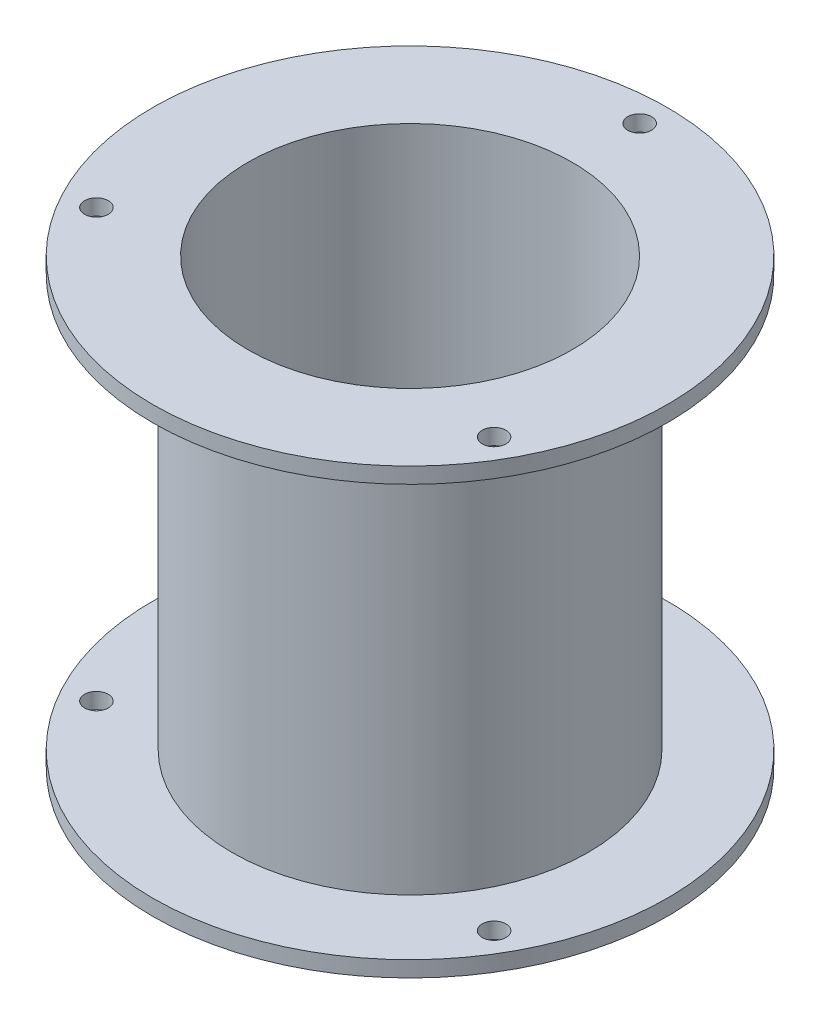
SolidWorks part; units mm, degrees
ref_plane "Front Plane" through (0, 0, 0) normal (0, 0, 1) x (1, 0, 0)
ref_plane "Top Plane" through (0, 0, 0) normal (0, 1, 0) x (1, 0, 0)
ref_plane "Right Plane" through (0, 0, 0) normal (1, 0, 0) x (0, 0, -1)
sketch "Sketch1" plane through (0, 0, 0) normal (0, 1, 0) x (1, 0, 0)
  circle A4 centre (0, 0) radius 32.5
  dimension "D5" = 65
extrude "Boss-Extrude1" add sketch "Sketch1" along normal blind 56
sketch "Sketch6" plane through (0, 56, 0) normal (0, 1, 0) x (1, 0, 0)
  circle A0 centre (0, 0) radius 22.5
  circle A1 centre (0, 0) radius 32.5 construction
  circle A2 centre (0, 0) radius 32.5
  dimension "D1" = 10
extrude "Cut-Extrude4" cut sketch "Sketch6" against normal offset from surface (52 mm away) 2 from offset 2 up to face at (0, 0, 32.5) offset against normal yes
sketch "Sketch2" plane through (0, 56, 0) normal (0, 1, 0) x (1, 0, 0)
  line L0 (0, 29) -> (0, 0) construction
  line L1 (0, 0) -> (-25.1147, -14.5) construction
  line L2 (0, 0) -> (25.1147, -14.5) construction
  circle A0 centre (0, 0) radius 29 construction
  circle A1 centre (0, 29) radius 1.5
  circle A2 centre (-25.1147, -14.5) radius 1.5
  circle A3 centre (25.1147, -14.5) radius 1.5
  point P9 (0, 29)
  point P10 (25.1147, -14.5)
  dimension "D1" = 58
  dimension "D4" = 3
  dimension "D2" = 120
  dimension "D3" = 120
extrude "Cut-Extrude2" cut sketch "Sketch2" against normal through all
sketch "Sketch5" plane through (0, 56, 0) normal (0, 1, 0) x (1, 0, 0)
  circle A0 centre (0, 0) radius 25.5
  circle A1 centre (0, 0) radius 32.5 construction
  dimension "6" = 7
extrude "Cut-Extrude3" [suppressed] cut sketch "Sketch5" against normal up to next
shell "Shell1" thickness 2 removed face at (0, 56, -27.5) removed face at (0, 0, -27.5)
equation "\"D1@Sketch2\"=29*2"
